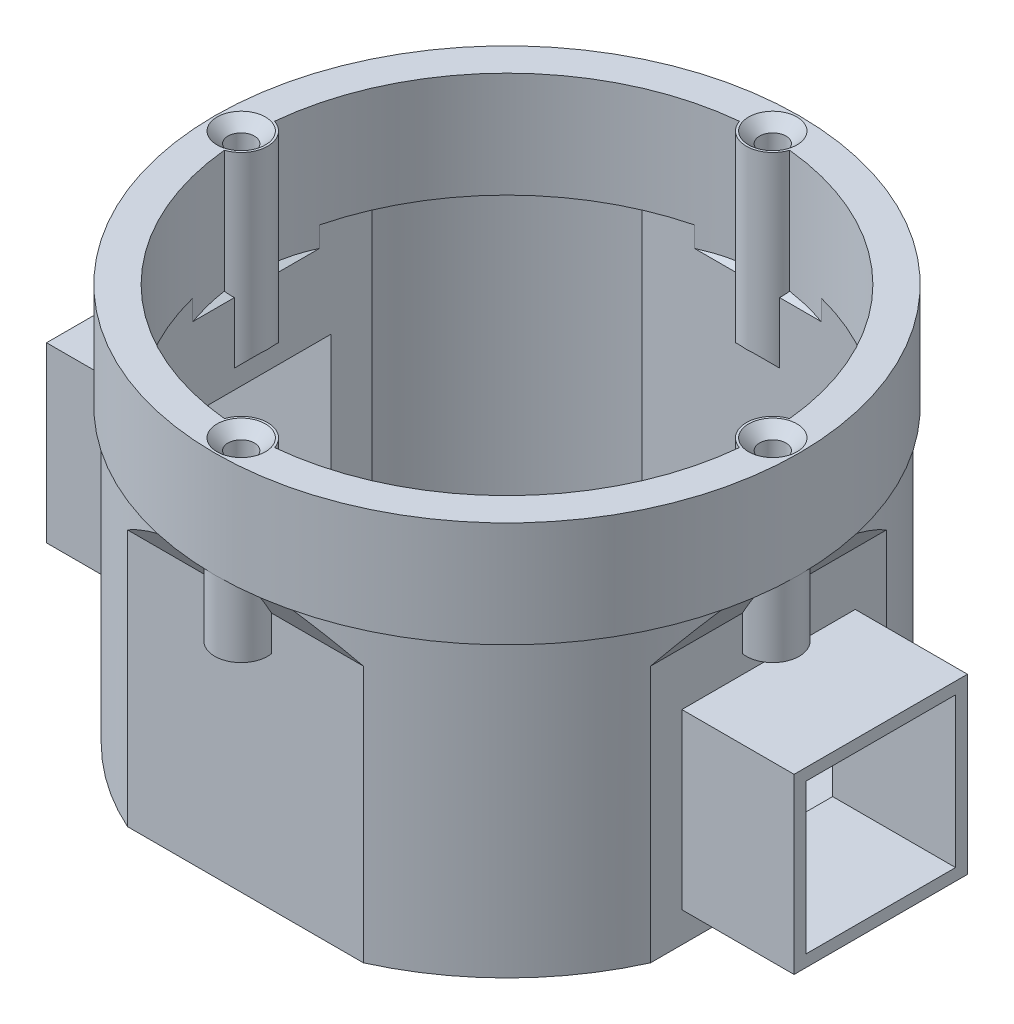
SolidWorks part; units mm, degrees
ref_plane "Front Plane" through (0, 0, 0) normal (0, 0, 1) x (1, 0, 0)
ref_plane "Top Plane" through (0, 0, 0) normal (0, 1, 0) x (1, 0, 0)
ref_plane "Right Plane" through (0, 0, 0) normal (1, 0, 0) x (0, 0, -1)
sketch "Sketch1" plane through (0, 0, 0) normal (0, 1, 0) x (1, 0, 0)
  line L0 (0, 56.9645) -> (0, 31.3824) construction
  line L1 (-45.9391, 0) -> (-31.3824, 0) construction
  line L2 (28.5, 13.1378) -> (28.5, -13.1378)
  line L3 (-28.5, 13.1378) -> (-28.5, -13.1378)
  line L4 (-13.1378, 28.5) -> (13.1378, 28.5)
  line L5 (-13.1378, -28.5) -> (13.1378, -28.5)
  line L6 (0, 31.3824) -> (0, 28.5) construction
  line L7 (0, 28.5) -> (0, -28.5) construction
  line L8 (-31.3824, 0) -> (-28.5, 0) construction
  line L9 (-28.5, 0) -> (28.5, 0) construction
  line L10 (0, -28.5) -> (0, -31.3824) construction
  line L11 (0, -31.3824) -> (0, -56.9645) construction
  line L12 (28.5, 0) -> (31.3824, 0) construction
  line L13 (31.3824, 0) -> (57.4239, 0) construction
  arc A0 (-13.1378, 28.5) -> (-28.5, 13.1378) centre (0, 0) ccw
  arc A1 (0, 31.3824) -> (-13.1378, 28.5) centre (0, 0) ccw construction
  arc A2 (13.1378, 28.5) -> (0, 31.3824) centre (0, 0) ccw construction
  arc A3 (-28.5, 13.1378) -> (-31.3824, 0) centre (0, 0) ccw construction
  arc A4 (-28.5, -13.1378) -> (-13.1378, -28.5) centre (0, 0) ccw
  arc A5 (-31.3824, 0) -> (-28.5, -13.1378) centre (0, 0) ccw construction
  arc A6 (-13.1378, -28.5) -> (0, -31.3824) centre (0, 0) ccw construction
  arc A7 (13.1378, -28.5) -> (28.5, -13.1378) centre (0, 0) ccw
  arc A8 (0, -31.3824) -> (13.1378, -28.5) centre (0, 0) ccw construction
  arc A9 (28.5, -13.1378) -> (31.3824, 0) centre (0, 0) ccw construction
  arc A10 (28.5, 13.1378) -> (13.1378, 28.5) centre (0, 0) ccw
  arc A11 (31.3824, 0) -> (28.5, 13.1378) centre (0, 0) ccw construction
  dimension "D1" = 28.5
  dimension "D2" = 57
extrude "Extrude-Thin1" add sketch "Sketch1" along normal blind 32 thin thin type one direction wall 1.22
sketch "Sketch2" plane through (0, 32, 0) normal (0, 1, 0) x (1, 0, 0)
  line L8 (0, 33.2) -> (0, -33.2) construction
  line L9 (-33.2, 0) -> (33.2, 0) construction
  circle A0 centre (0, 0) radius 33.2
  circle A9 centre (0, 0) radius 29.4
  point P17 (0, 0)
  dimension "D1" = 3.8
extrude "Boss-Extrude1" add sketch "Sketch2" along normal blind 12
chamfer "Chamfer1" distance 4 angle 30 8 edges at (0, 32, -28.5) (0, 32, 28.5) (-28.5, 32, 0) (28.5, 32, 0) (0, 32, -29.72) (-29.72, 32, 0) (0, 32, 29.72) (29.72, 32, 0) first distance on face at (0, 32, -28.95) first distance on face at (0, 32, 28.95) first distance on face at (-28.95, 32, 0) first distance on face at (28.95, 32, 0) first distance on face at (0, 16, -29.72) first distance on face at (-29.72, 16, 0) first distance on face at (0, 16, 29.72) first distance on face at (29.72, 16, 0)
sketch "Sketch3" plane through (0, 44, 0) normal (0, 1, 0) x (1, 0, 0)
  line L0 (0, 35.6936) -> (0, -37.253) construction
  line L1 (-39.6788, 0) -> (43.4907, 0) construction
  circle A4 centre (0, 30.2) radius 3
  circle A5 centre (30.2, 0) radius 3
  circle A6 centre (0, -30.2) radius 3
  circle A7 centre (-30.2, 0) radius 3
  circle A8 centre (0, 0) radius 33.2 construction
  point P6 (0, 0)
  point P8 (0, 29.9863)
  point P16 (0, 0)
  point P24 (0, 0)
  dimension "D3" = 6
  dimension "D4" = 4
extrude "Boss-Extrude2" add sketch "Sketch3" against normal blind 20
chamfer "Chamfer2" distance 1.25 angle 45 4 edges at (-28.5, 24, 0) (0, 24, 28.5) (28.5, 24, 0) (0, 24, -28.5)
sketch "Sketch5" plane through (-29.72, 0, 0) normal (-1, 0, 0) x (0, 0, 1)
  line L0 (0, 44) -> (0, 0) construction
  line L1 (2.8495, 44) -> (-2.8495, 44) construction
  line L2 (-29.72, 0) -> (-13.4028, 0) construction
  line L3 (-9.85, 21.95) -> (9.85, 21.95)
  line L4 (-9.85, 21.95) -> (-9.85, 2.25)
  line L5 (-9.85, 2.25) -> (9.85, 2.25)
  line L6 (9.85, 21.95) -> (9.85, 2.25)
  line L7 (-9.85, 21.95) -> (9.85, 2.25) construction
  line L8 (-9.85, 2.25) -> (9.85, 21.95) construction
  point P5 (0, 12.1)
  point P10 (0, 0)
  point P11 (0, 7.3369)
  dimension "D1" = 19.7
  dimension "D2" = 19.7
  dimension "D3" = 2.25
extrude "Boss-Extrude3" add sketch "Sketch5" along normal blind 12.75
mirror "Mirror1" about plane through (0, 0, 0) normal (1, 0, 0) of "Boss-Extrude3"
sketch "Sketch6" plane through (-42.47, 0, 0) normal (-1, 0, 0) x (0, 0, 1)
  line L1 (-8.5, 3.6) -> (8.5, 3.6)
  line L2 (-8.5, 3.6) -> (-8.5, 20.6)
  line L3 (-8.5, 20.6) -> (8.5, 20.6)
  line L4 (8.5, 3.6) -> (8.5, 20.6)
  line L5 (-8.5, 3.6) -> (8.5, 20.6) construction
  line L6 (-8.5, 20.6) -> (8.5, 3.6) construction
  point P0 (0, 12.1)
  dimension "D1" = 17
extrude "Cut-Extrude1" cut sketch "Sketch6" against normal through all both and the other way through all
sketch "Sketch7" plane through (0, 0, 0) normal (0, -1, 0) x (1, 0, 0)
  line L4 (29.72, -13.4028) -> (29.72, 13.4028)
  line L5 (13.4028, 29.72) -> (-13.4028, 29.72)
  line L6 (-29.72, 13.4028) -> (-29.72, -13.4028)
  line L7 (-13.4028, -29.72) -> (13.4028, -29.72)
  line L8 (29.72, -13.4028) -> (29.72, 13.4028)
  line L9 (13.4028, 29.72) -> (-13.4028, 29.72)
  line L10 (-29.72, 13.4028) -> (-29.72, -13.4028)
  line L11 (-13.4028, -29.72) -> (13.4028, -29.72)
  arc A4 (13.4028, -29.72) -> (29.72, -13.4028) centre (0, 0) ccw
  arc A5 (29.72, 13.4028) -> (13.4028, 29.72) centre (0, 0) ccw
  arc A6 (-13.4028, 29.72) -> (-29.72, 13.4028) centre (0, 0) ccw
  arc A7 (-29.72, -13.4028) -> (-13.4028, -29.72) centre (0, 0) ccw
  arc A8 (13.4028, -29.72) -> (29.72, -13.4028) centre (0, 0) ccw
  arc A9 (29.72, 13.4028) -> (13.4028, 29.72) centre (0, 0) ccw
  arc A10 (-13.4028, 29.72) -> (-29.72, 13.4028) centre (0, 0) ccw
  arc A11 (-29.72, -13.4028) -> (-13.4028, -29.72) centre (0, 0) ccw
  dimension "D1" = 0
extrude "Boss-Extrude4" add sketch "Sketch7" along normal blind 1.2
sketch "Sketch8" plane through (0, 44, 0) normal (0, 1, 0) x (1, 0, 0)
  circle A0 centre (0, 30.2) radius 1.5
  circle A1 centre (30.2, 0) radius 1.5
  circle A2 centre (0, -30.2) radius 1.5
  circle A3 centre (-30.2, 0) radius 1.5
  point P12 (0, 0)
  dimension "D1" = 3
  dimension "D2" = 4
extrude "Cut-Extrude2" cut sketch "Sketch8" against normal blind 15
chamfer "Chamfer3" distance 1.25 angle 45 4 edges at (30.2, 44, 1.5) (0, 44, 31.7) (-30.2, 44, 1.5) (0, 44, -28.7)
